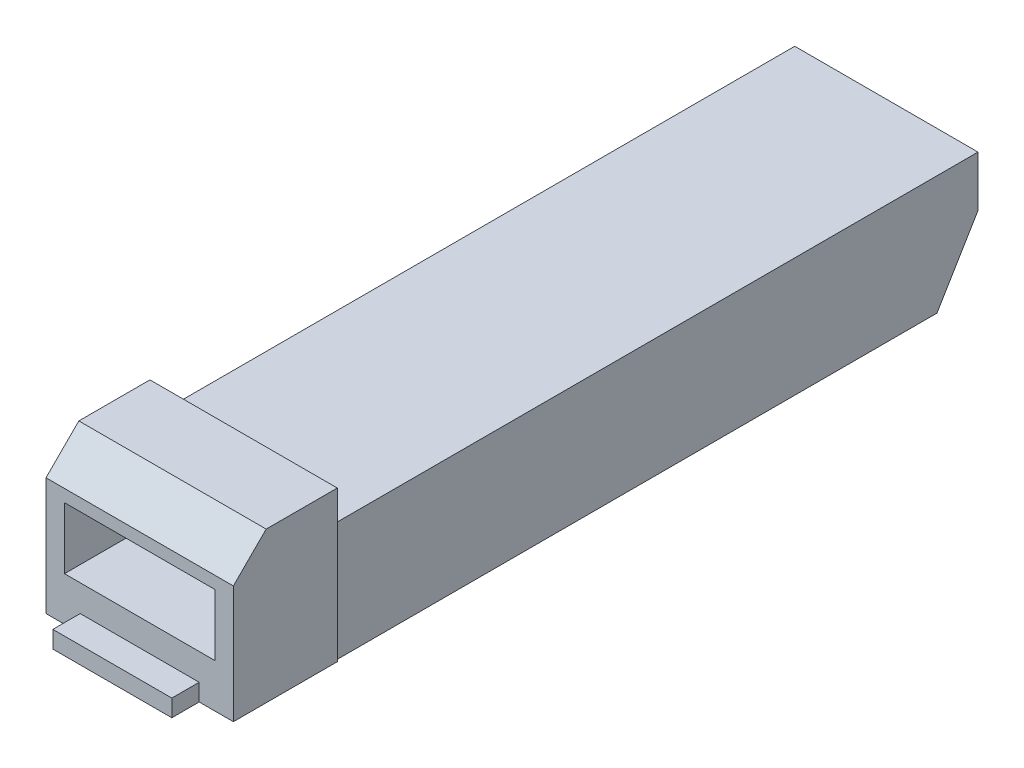
SolidWorks part; units mm, degrees
ref_plane "Front" through (0, 0, 0) normal (0, 0, 1) x (1, 0, 0)
ref_plane "Top" through (0, 0, 0) normal (0, 1, 0) x (1, 0, 0)
ref_plane "Right" through (0, 0, 0) normal (1, 0, 0) x (0, 0, -1)
sketch "Sketch1" plane through (0, 0, 0) normal (0, 1, 0) x (1, 0, 0)
  line L1 (-6.7, 16.9702) -> (6.7, 16.9702)
  line L2 (-6.7, 16.9702) -> (-6.7, -30.0298)
  line L3 (-6.7, -30.0298) -> (6.7, -30.0298)
  line L4 (6.7, 16.9702) -> (6.7, -30.0298)
extrude "Boss-Extrude1" add sketch "Sketch1" along normal blind 8.7
sketch "Sketch2" plane through (-6.7, 0, 0) normal (-1, 0, 0) x (0, 0, 1)
  line L0 (-16.9702, 0) -> (-16.9702, 5)
  line L1 (-16.9702, 8.7) -> (-16.9702, 0) construction
  line L2 (-16.9702, 0) -> (-13.9702, 0)
  line L3 (-16.9702, 0) -> (30.0298, 0) construction
  line L4 (-13.9702, 0) -> (-16.9702, 5)
extrude "Cut-Extrude1" cut sketch "Sketch2" against normal through all
sketch "Sketch3" plane through (0, 0, 30.0298) normal (0, 0, 1) x (1, 0, 0)
  line L0 (-6.7, 0) -> (6.7, 0) construction
  line L1 (-6.85, 11) -> (6.85, 11)
  line L2 (-6.85, 11) -> (-6.85, 0)
  line L3 (-6.85, 0) -> (6.85, 0)
  line L4 (6.85, 11) -> (6.85, 0)
extrude "Boss-Extrude2" add sketch "Sketch3" along normal blind 7.6 contours L1 L4 L3 L2
sketch "Sketch4" plane through (-6.85, 0, 0) normal (-1, 0, 0) x (0, 0, 1)
  line L0 (37.6298, 11) -> (35.2298, 11)
  line L1 (37.6298, 11) -> (30.0298, 11) construction
  line L2 (37.6298, 11) -> (37.6298, 8.6)
  line L3 (37.6298, 11) -> (37.6298, 0) construction
  line L4 (37.6298, 8.6) -> (35.2298, 11)
extrude "Cut-Extrude2" cut sketch "Sketch4" against normal through all
sketch "Sketch5" plane through (0, 0, 37.6298) normal (0, 0, 1) x (1, 0, 0)
  line L1 (4.35, 0) -> (-4.35, 0)
  line L2 (4.35, 0) -> (4.35, 1.25)
  line L3 (4.35, 1.25) -> (-4.35, 1.25)
  line L4 (-4.35, 0) -> (-4.35, 1.25)
extrude "Boss-Extrude3" add sketch "Sketch5" along normal blind 2 separate body
ref_plane "Plane1" through (0, 17.8111, 11.132) normal (0, 0.848, 0.53) x (1, 0, 0)
ref_plane "Plane2" through (0, -16.9123, 10.5702) normal (0, -0.848, 0.53) x (-1, 0, 0)
ref_axis "Axis1" through (-24.8973, 0.625, 38.6298) along (1, 0, 0)
sketch "Sketch7" plane through (0, 0, 37.6298) normal (0, 0, 1) x (1, 0, 0)
  line L1 (-5.5, 7.7) -> (5.5, 7.7)
  line L2 (-5.5, 7.7) -> (-5.5, 3.2)
  line L3 (-5.5, 3.2) -> (5.5, 3.2)
  line L4 (5.5, 7.7) -> (5.5, 3.2)
extrude "Cut-Extrude3" cut sketch "Sketch7" against normal blind 9.5 contours L3 L4 L1 L2
